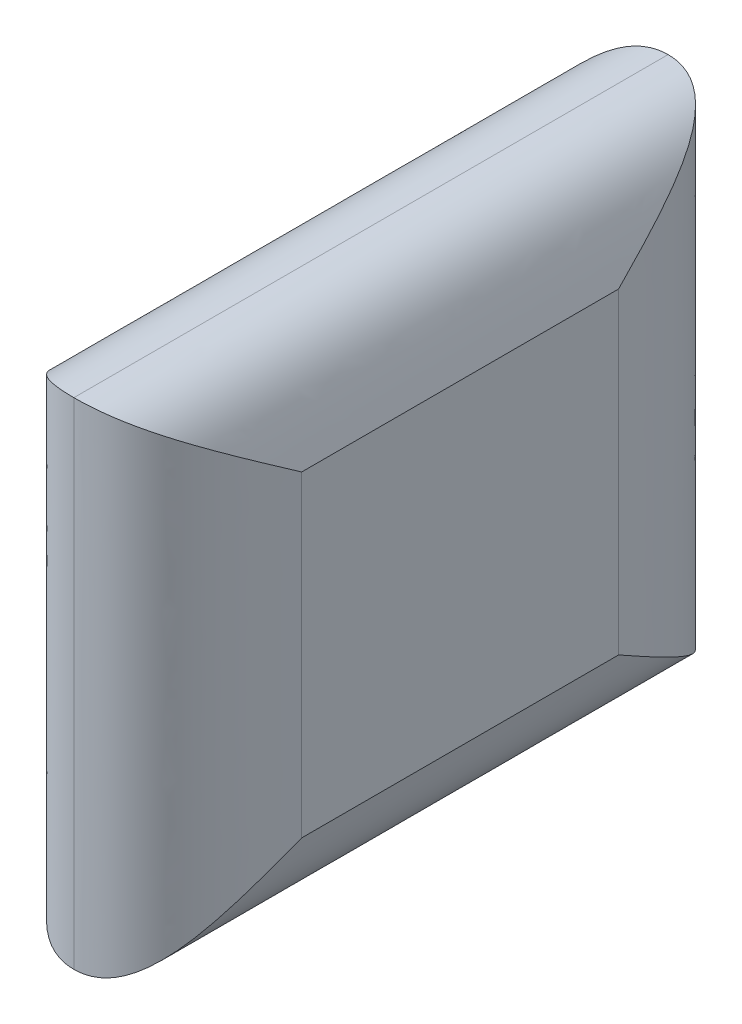
SolidWorks part; units mm, degrees
ref_plane "Front Plane" through (0, 0, 0) normal (0, 0, 1) x (1, 0, 0)
ref_plane "Top Plane" through (0, 0, 0) normal (0, 1, 0) x (1, 0, 0)
ref_plane "Right Plane" through (0, 0, 0) normal (1, 0, 0) x (0, 0, -1)
sketch "Sketch1" plane through (200, 0, 0) normal (1, 0, 0) x (0, 0, -1)
  line L1 (150, 0) -> (150, 125) construction
  line L2 (150, 125) -> (0, 125) construction
  line L8 (35, 102.5) -> (35, 22.5)
  line L9 (35, 22.5) -> (115, 22.5)
  line L10 (115, 22.5) -> (115, 102.5)
  line L11 (115, 102.5) -> (35, 102.5)
  point P2 (0, 0)
  point P4 (0, 80)
  point P9 (80, 80)
  dimension "D1" = 80
  dimension "D2" = 80
  dimension "D3" = 35
  dimension "D4" = 22.5
ref_plane "Plane1" through (222.5, 0, 0) normal (1, 0, 0) x (0, 0, -1)
sketch "Sketch2" plane through (222.5, 0, 0) normal (1, 0, 0) x (0, 0, -1)
  line L4 (0, 125) -> (0, 0)
  line L5 (0, 0) -> (150, 0)
  line L6 (150, 0) -> (150, 125)
  line L7 (150, 125) -> (0, 125)
  line L8 (0, 125) -> (0, 0)
  line L9 (0, 0) -> (150, 0)
  line L10 (150, 0) -> (150, 125)
  line L11 (150, 125) -> (0, 125)
  dimension "D1" = 0
loft "Loft1" add profiles "Sketch1", "Sketch2" end constraint normal to profile end tangent length 1 connector at (200, 102.5, -115) connector at (222.5, 125, -150)
mirror "Mirror1" about plane through (222.5, 0, 0) normal (1, 0, 0) of "Loft1"
